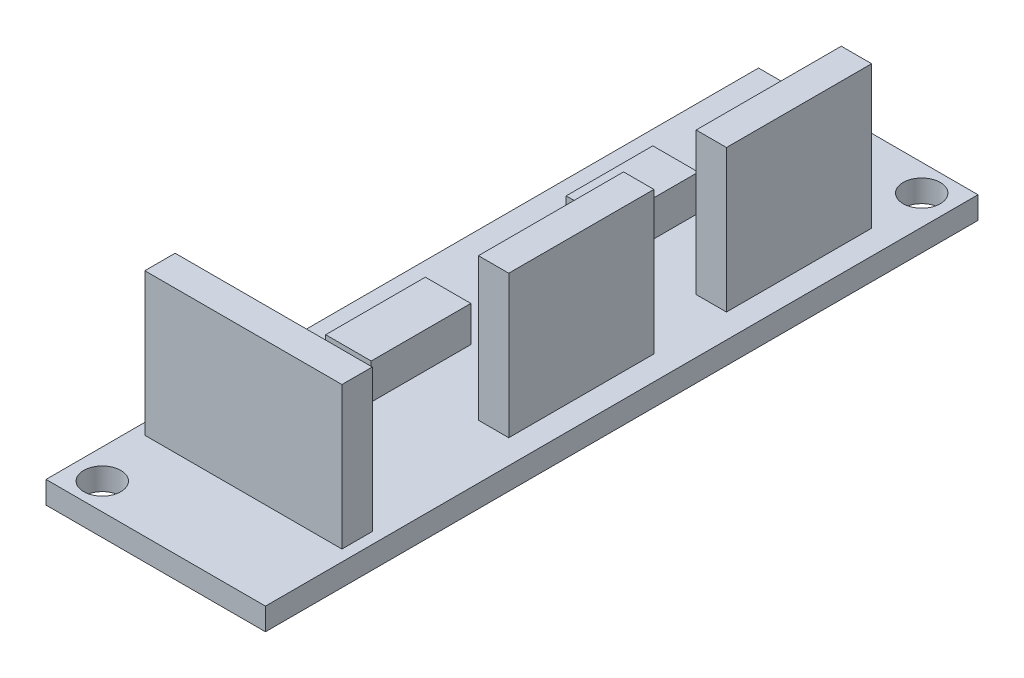
SolidWorks part; units mm, degrees
ref_plane "Front Plane" through (0, 0, 0) normal (0, 0, 1) x (1, 0, 0)
ref_plane "Top Plane" through (0, 0, 0) normal (0, 1, 0) x (1, 0, 0)
ref_plane "Right Plane" through (0, 0, 0) normal (1, 0, 0) x (0, 0, -1)
sketch "Sketch1" plane through (0, 0, 0) normal (0, 1, 0) x (1, 0, 0)
  line L1 (-9.779, 31.75) -> (9.779, 31.75)
  line L2 (-9.779, 31.75) -> (-9.779, -31.75)
  line L3 (-9.779, -31.75) -> (9.779, -31.75)
  line L4 (9.779, 31.75) -> (9.779, -31.75)
  line L5 (-9.779, 31.75) -> (9.779, -31.75) construction
  line L6 (-9.779, -31.75) -> (9.779, 31.75) construction
  line L7 (7.1437, -29.3688) -> (-7.1438, -29.3688) construction
  line L8 (7.1437, -29.3688) -> (7.1437, 29.3687) construction
  line L9 (7.1437, 29.3687) -> (-7.1438, 29.3687) construction
  line L10 (-7.1438, -29.3688) -> (-7.1438, 29.3687) construction
  line L11 (7.1437, -29.3688) -> (-7.1438, 29.3687) construction
  line L12 (7.1437, 29.3687) -> (-7.1438, -29.3688) construction
  circle A0 centre (7.1437, 29.3687) radius 1.651
  circle A1 centre (-7.1438, -29.3688) radius 1.651
  point P0 (0, 0)
  point P6 (0, 0)
  dimension "D5" = 3.302
  dimension "D1" = 63.5
  dimension "D2" = 19.558
  dimension "D3" = 58.7375
  dimension "D4" = 14.2875
extrude "Boss-Extrude1" add sketch "Sketch1" along normal blind 1.9844
sketch "Sketch2" plane through (0, 1.9844, 0) normal (0, 1, 0) x (1, 0, 0)
  line L0 (0, -31.75) -> (0, -22.5887) construction
  line L1 (-9.779, -31.75) -> (9.779, -31.75) construction
  line L3 (-8.7845, -23.9402) -> (8.7845, -23.9402)
  line L4 (-8.7845, -23.9402) -> (-8.7845, -21.2373)
  line L5 (-8.7845, -21.2373) -> (8.7845, -21.2373)
  line L6 (8.7845, -23.9402) -> (8.7845, -21.2373)
  line L7 (-8.7845, -23.9402) -> (8.7845, -21.2373) construction
  line L8 (-8.7845, -21.2373) -> (8.7845, -23.9402) construction
  line L9 (-5.3093, 17.8586) -> (-1.2549, 17.8586)
  line L10 (-5.3093, 17.8586) -> (-5.3093, 10.136)
  line L11 (-5.3093, 10.136) -> (-1.2549, 10.136)
  line L12 (-1.2549, 17.8586) -> (-1.2549, 10.136)
  line L13 (-5.3093, 17.8586) -> (-1.2549, 10.136) construction
  line L14 (-5.3093, 10.136) -> (-1.2549, 17.8586) construction
  line L15 (-5.3093, -2.4133) -> (-1.2549, -2.4133)
  line L16 (-5.3093, -2.4133) -> (-5.3093, -11.2944)
  line L17 (-5.3093, -11.2944) -> (-1.2549, -11.2944)
  line L18 (-1.2549, -2.4133) -> (-1.2549, -11.2944)
  line L19 (-5.3093, -2.4133) -> (-1.2549, -11.2944) construction
  line L20 (-5.3093, -11.2944) -> (-1.2549, -2.4133) construction
  line L21 (4.9232, 24.4229) -> (7.6261, 24.4229)
  line L22 (4.9232, 24.4229) -> (4.9232, 11.4874)
  line L23 (4.9232, 11.4874) -> (7.6261, 11.4874)
  line L24 (7.6261, 24.4229) -> (7.6261, 11.4874)
  line L25 (4.9232, 5.0197) -> (7.6261, 5.0197)
  line L26 (4.9232, 5.0197) -> (4.9232, -7.9157)
  line L27 (4.9232, -7.9157) -> (7.6261, -7.9157)
  line L28 (7.6261, 5.0197) -> (7.6261, -7.9157)
  point P9 (-3.2821, 13.9973)
  point P14 (-3.2821, -6.8538)
extrude "Boss-Extrude3" add sketch "Sketch2" along normal blind 12.7 contours L22 L23 L24 L21 | L26 L27 L28 L25 | L3 L6 L5 L4
extrude "Boss-Extrude4" add sketch "Sketch2<3>" along normal blind 3.175 contours L16 L17 L18 L15 | L10 L11 L12 L9
sketch "Sketch2<3>" plane through (0, 1.9844, 0) normal (0, 1, 0) x (1, 0, 0) same geometry as "Sketch2"
